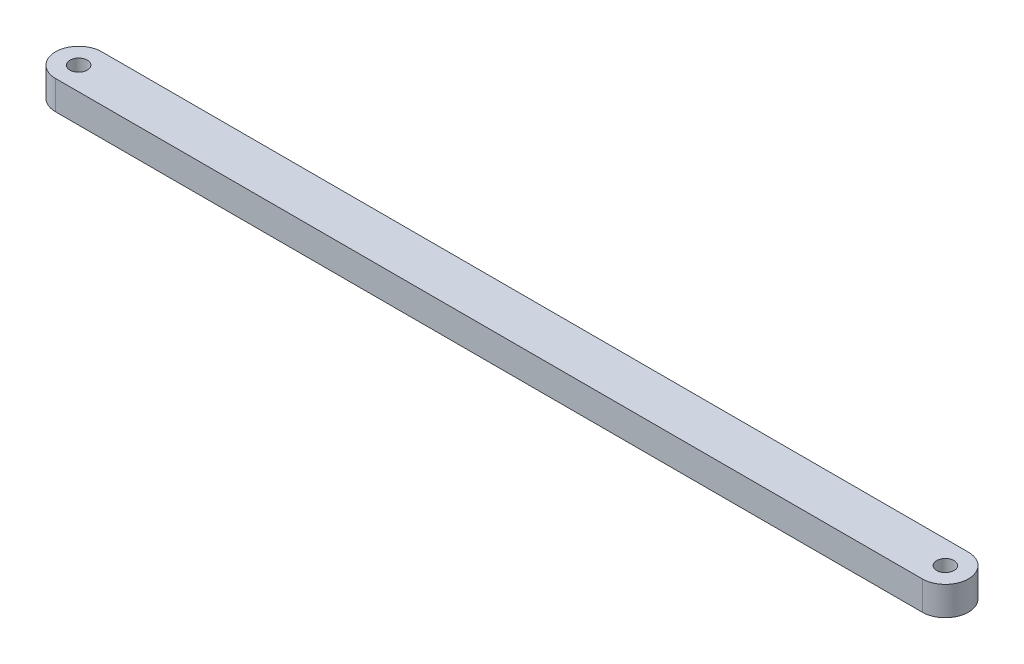
SolidWorks part; units mm, degrees
ref_plane "Front Plane" through (0, 0, 0) normal (0, 0, 1) x (1, 0, 0)
ref_plane "Top Plane" through (0, 0, 0) normal (0, 1, 0) x (1, 0, 0)
ref_plane "Right Plane" through (0, 0, 0) normal (1, 0, 0) x (0, 0, -1)
sketch "Sketch1" plane through (0, 0, 0) normal (0, 1, 0) x (1, 0, 0)
  line L0 (-75, 0) -> (75, 0) construction
  line L1 (-75, 4) -> (75, 4)
  line L2 (-75, -4) -> (75, -4)
  arc A0 (-75, 4) -> (-75, -4) centre (-75, 0) ccw
  arc A1 (75, -4) -> (75, 4) centre (75, 0) ccw
  circle A2 centre (-75, 0) radius 1.5
  circle A3 centre (75, 0) radius 1.5
  point P3 (0, 0)
  dimension "D2" = 4
  dimension "D3" = 3
  dimension "D1" = 150
extrude "Boss-Extrude1" add sketch "Sketch1" along normal blind 5 contours L2 A1 L1 A0 | A3 | A2
